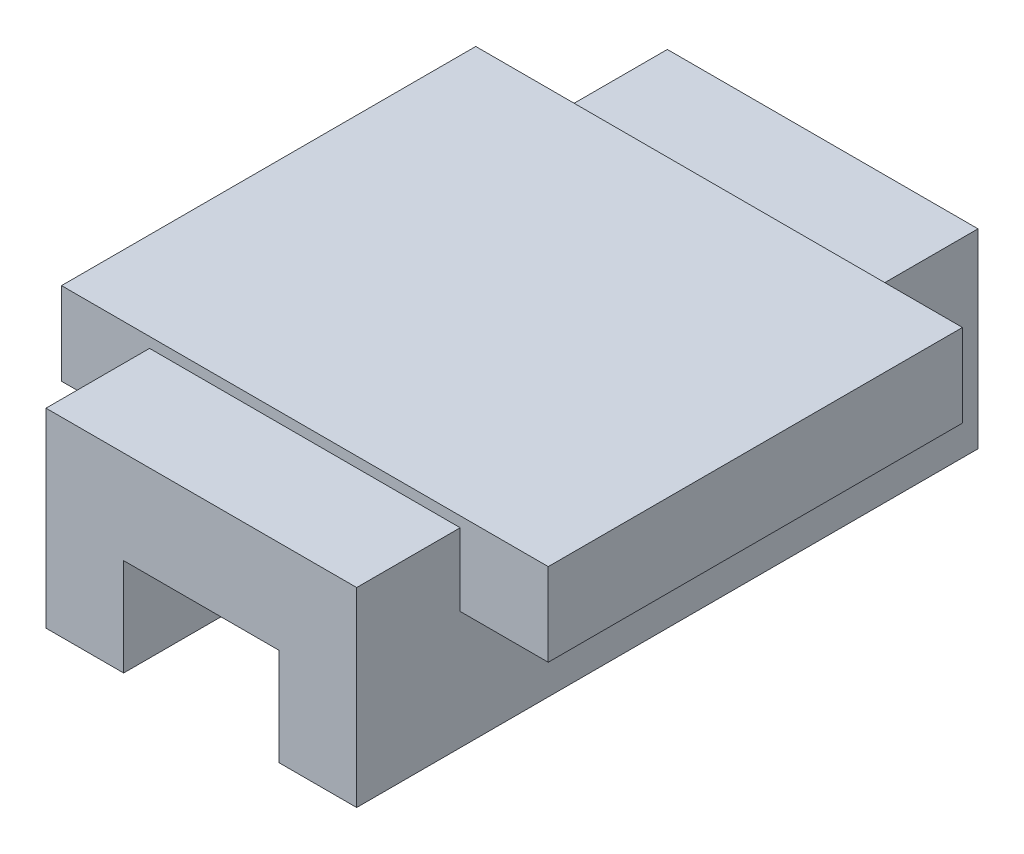
SolidWorks part; units mm, degrees
ref_plane "Front Plane" through (0, 0, 0) normal (0, 0, 1) x (1, 0, 0)
ref_plane "Top Plane" through (0, 0, 0) normal (0, 1, 0) x (1, 0, 0)
ref_plane "Right Plane" through (0, 0, 0) normal (1, 0, 0) x (0, 0, -1)
sketch "Sketch1" plane through (0, 0, 0) normal (0, 0, 1) x (1, 0, 0)
  line L0 (0, -30.2326) -> (0, 30.2326) construction
  line L1 (7.5, -7) -> (-7.5, -7)
  line L2 (7.5, -7) -> (7.5, 7)
  line L3 (7.5, 7) -> (-7.5, 7)
  line L4 (-7.5, -7) -> (-7.5, 7)
  line L5 (7.5, -7) -> (-7.5, 7) construction
  line L6 (7.5, 7) -> (-7.5, -7) construction
  line L8 (15, -2.4) -> (-15, -2.4)
  line L9 (15, -2.4) -> (15, 16)
  line L10 (15, 16) -> (-15, 16)
  line L11 (-15, -2.4) -> (-15, 16)
  line L12 (15, -2.4) -> (-15, 16) construction
  line L13 (15, 16) -> (-15, -2.4) construction
  line L14 (23.5, 9) -> (-23.5, 9)
  line L15 (23.5, 9) -> (23.5, 17)
  line L16 (23.5, 17) -> (-23.5, 17)
  line L17 (-23.5, 9) -> (-23.5, 17)
  line L18 (23.5, 9) -> (-23.5, 17) construction
  line L19 (23.5, 17) -> (-23.5, 9) construction
  point P0 (0, 0)
  point P8 (0, 6.8)
  point P13 (0, 13)
  dimension "D1" = 15
  dimension "D2" = 4.6
  dimension "D3" = 14
  dimension "D4" = 24
  dimension "D5" = 30
  dimension "D6" = 1
  dimension "D7" = 8
  dimension "D8" = 47
extrude "Boss-Extrude1" add sketch "Sketch1" along normal mid plane 60 contours L9 L14 L11 L8 L4 L3 L2 | L14 L9 L10 L11 region at (7.8209, 2.3, 0) region at (0, 12.5, 0)
extrude "Boss-Extrude2" add sketch "Sketch1<3>" along normal mid plane 40 contours L17 L14 L11 L10 L9 L15 L16 region at (15.4768, 12.5, 0)
sketch "Sketch1<3>" plane through (0, 0, 0) normal (0, 0, 1) x (1, 0, 0) same geometry as "Sketch1"
